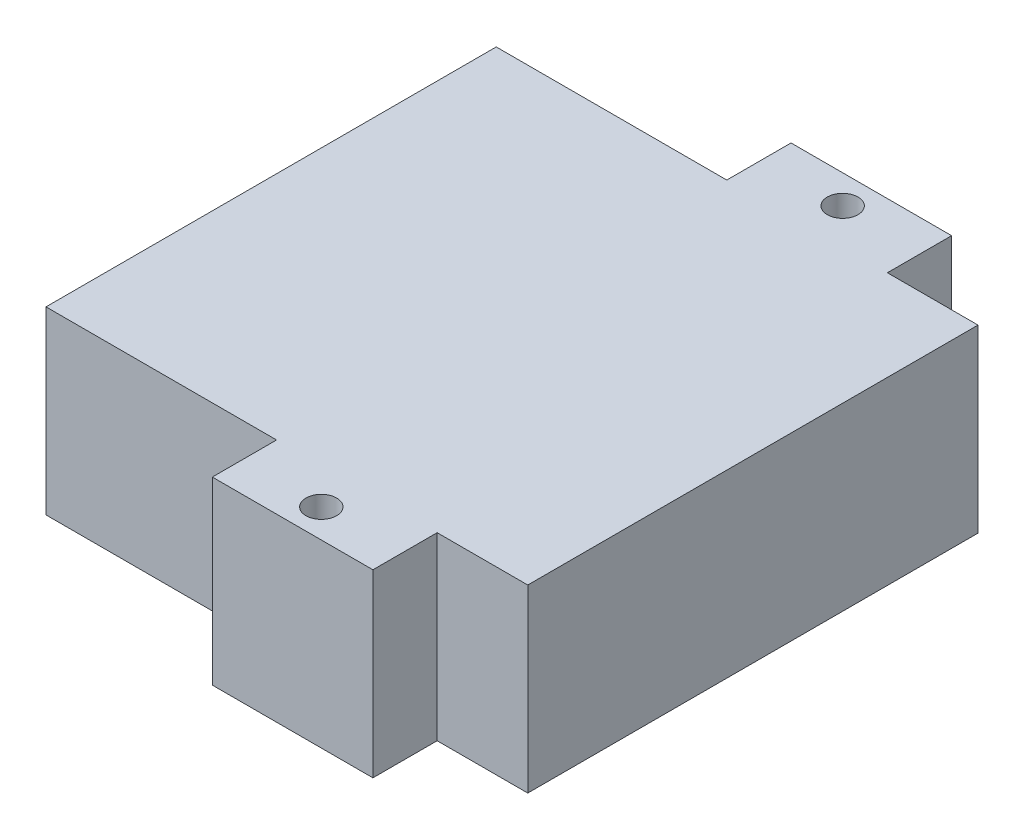
SolidWorks part; units mm, degrees
ref_plane "Front Plane" through (0, 0, 0) normal (0, 0, 1) x (1, 0, 0)
ref_plane "Top Plane" through (0, 0, 0) normal (0, 1, 0) x (1, 0, 0)
ref_plane "Right Plane" through (0, 0, 0) normal (1, 0, 0) x (0, 0, -1)
sketch "Sketch1" plane through (0, 0, 0) normal (0, 1, 0) x (1, 0, 0)
  line L0 (16.637, 24.9238) -> (26.67, 24.9238)
  line L1 (-26.67, -24.9237) -> (-1.143, -24.9238)
  line L2 (-26.67, -24.9237) -> (-26.67, 24.9238)
  line L3 (-26.67, 24.9238) -> (-1.143, 24.9238)
  line L4 (26.67, -24.9237) -> (26.67, 24.9238)
  line L5 (-26.67, -24.9237) -> (26.67, 24.9238) construction
  line L6 (-26.67, 24.9238) -> (26.67, -24.9237) construction
  line L8 (-1.143, 24.9238) -> (-1.143, 32.0358)
  line L9 (-1.143, 32.0358) -> (16.637, 32.0358)
  line L10 (16.637, 24.9238) -> (16.637, 32.0358)
  line L11 (0, 0) -> (26.67, 0) construction
  line L12 (16.637, -24.9237) -> (16.637, -32.0358)
  line L13 (-1.143, -32.0358) -> (16.637, -32.0358)
  line L14 (-1.143, -24.9238) -> (-1.143, -32.0358)
  line L15 (16.637, -24.9237) -> (26.67, -24.9237)
  point P0 (0, 0)
  dimension "D1" = 53.34
  dimension "D2" = 49.8475
  dimension "D3" = 17.78
  dimension "D4" = 10.033
  dimension "D5" = 7.112
extrude "Boss-Extrude1" add sketch "Sketch1" along normal blind 19.9517
sketch "Sketch3" plane through (0, 19.9517, 0) normal (0, 1, 0) x (1, 0, 0)
  line L0 (16.637, 32.0358) -> (-1.143, 32.0358) construction
  line L1 (-1.143, 32.0358) -> (-1.143, 24.9238) construction
  line L2 (0, 0) -> (26.67, 0) construction
  line L3 (26.67, -24.9237) -> (26.67, 24.9238) construction
  point P0 (7.747, 28.8607)
  point P3 (7.747, -28.8607)
  dimension "D1" = 3.175
  dimension "D2" = 8.89
hole_wizard "M3 Clearance Hole1" positions "Sketch4" profile "Sketch5" hole size "M3" standard "ANSI Metric" end condition through all
sketch "Sketch4" plane through (0, 19.9517, 0) normal (0, 1, 0) x (1, 0, 0)
  point P0 (7.747, 28.8607)
  point P4 (7.747, -28.8607)
sketch "Sketch5" plane through (7.747, 19.9517, -28.8607) normal (1, 0, 0) x (0, 0, 1)
  line L0 (0, 0) -> (0, 19.9517)
  line L1 (0, 19.9517) -> (1.7, 19.9517)
  line L2 (1.7, 19.9517) -> (1.7, 0)
  line L5 (1.7, 0) -> (0, 0)
  line L11 (0, -6.35) -> (0, 107.95) construction
  dimension "Thru Hole Dia." = 3.4
  dimension "Thru Hole Depth" = 19.9517
